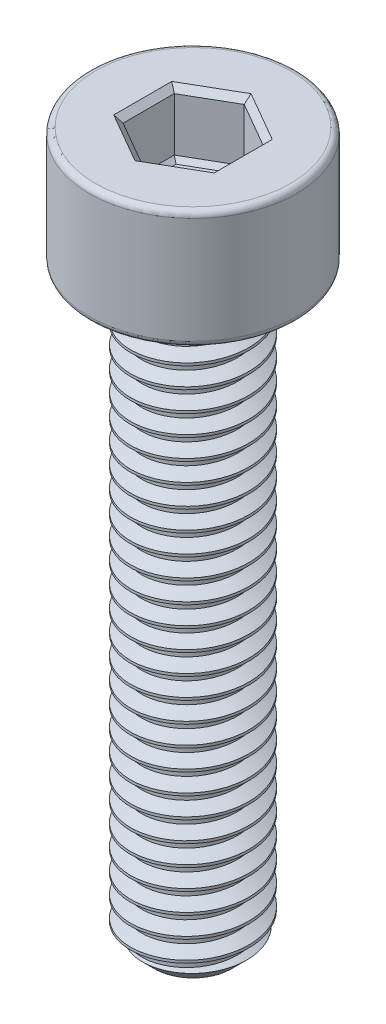
SolidWorks part; units mm, degrees
material "AISI Type A2 Tool Steel"
ref_plane "Front Plane" through (0, 0, 0) normal (0, 0, 1) x (1, 0, 0)
ref_plane "Top Plane" through (0, 0, 0) normal (0, 1, 0) x (1, 0, 0)
ref_plane "Right Plane" through (0, 0, 0) normal (1, 0, 0) x (0, 0, -1)
sketch "Sketch1" plane through (0, 0, 0) normal (0, 1, 0) x (1, 0, 0)
  circle A0 centre (0, 0) radius 2
  dimension "D1" = 4
extrude "Boss-Extrude1" add sketch "Sketch1" along normal blind 20
thread "Thread1" pitch 0.7 method cut profile "Thread Profile1" start angle 0, offset 1, length 0, pitch 0.7, diameter 4
ref_plane "Plane1" through (2, -1, 0) normal (0, 0, 1) x (1, 0, 0)
sketch "Thread Profile1" plane through (2, -1, 0) normal (0, 0, 1) x (1, 0, 0)
  line L0 (0, 0) -> (0, 0.7) construction
  line L11 (0, 0) -> (0, 0.6125)
  line L12 (0, 0.6125) -> (-0.3789, 0.3937)
  line L13 (-0.3789, 0.3937) -> (-0.3789, 0.2187)
  line L15 (-0.3789, 0.2187) -> (0, 0)
  line L17 (-0.3789, 0.3062) -> (0, 0.3062) construction
  point P2 (0, 0)
  dimension "Pitch" = 0.7
  dimension "Profile_Angle" = 60
  dimension "Profile_Land" = 0.175
  dimension "Profile_Height" = 0.3789
sketch "Sketch4" plane through (0, 20, 0) normal (0, -1, 0) x (-1, 0, 0)
  circle A0 centre (0, 0) radius 3.5
  dimension "D1" = 7
extrude "Boss-Extrude2" add sketch "Sketch4" against normal blind 4
fillet "Fillet1" radius 0.2 2 edges at (0, 20, -3.5) (0, 24, -3.5)
sketch "Sketch6" plane through (0, 0, 0) normal (0, 0, 1) x (1, 0, 0)
  line L0 (0, 0) -> (2.01, 0) construction
  line L1 (2.01, 0) -> (2.01, 0.7)
  line L2 (2.01, 0.7) -> (1.31, 0)
  line L3 (1.31, 0) -> (2.01, 0)
  line L4 (0, 0) -> (0, 0.3482) construction
  dimension "D1" = 0.7
  dimension "D2" = 45
  dimension "D3" = 2.01
revolve "Cut-Revolve1" cut sketch "Sketch6" angle 360 about L4
sketch "Sketch7" plane through (0, 24, 0) normal (0, 1, 0) x (1, 0, 0)
  line L1 (0, 1.7321) -> (-1.5, 0.866)
  line L2 (-1.5, 0.866) -> (-1.5, -0.866)
  line L3 (-1.5, -0.866) -> (0, -1.7321)
  line L4 (0, -1.7321) -> (1.5, -0.866)
  line L5 (1.5, -0.866) -> (1.5, 0.866)
  line L6 (1.5, 0.866) -> (0, 1.7321)
  circle A0 centre (0, 0) radius 1.5 construction
  dimension "D1" = 3
extrude "Cut-Extrude1" cut sketch "Sketch7" against normal blind 2
chamfer "Chamfer1" distance 0.2 angle 45 6 edges at (-1.5, 24, 0) (-0.75, 24, 1.299) (0.75, 24, 1.299) (1.5, 24, 0) (0.75, 24, -1.299) (-0.75, 24, -1.299)
sketch "Sketch8" plane through (0, 22, 0) normal (0, 1, 0) x (1, 0, 0)
  line L1 (0, 1.7321) -> (-1.5, 0.866)
  line L2 (-1.5, 0.866) -> (-1.5, -0.866)
  line L3 (-1.5, -0.866) -> (0, -1.7321)
  line L4 (0, -1.7321) -> (1.5, -0.866)
  line L5 (1.5, -0.866) -> (1.5, 0.866)
  line L6 (1.5, 0.866) -> (0, 1.7321)
  circle A0 centre (0, 0) radius 1.5 construction
extrude "Cut-Extrude2" cut sketch "Sketch8" against normal blind 0.15 draft 45
